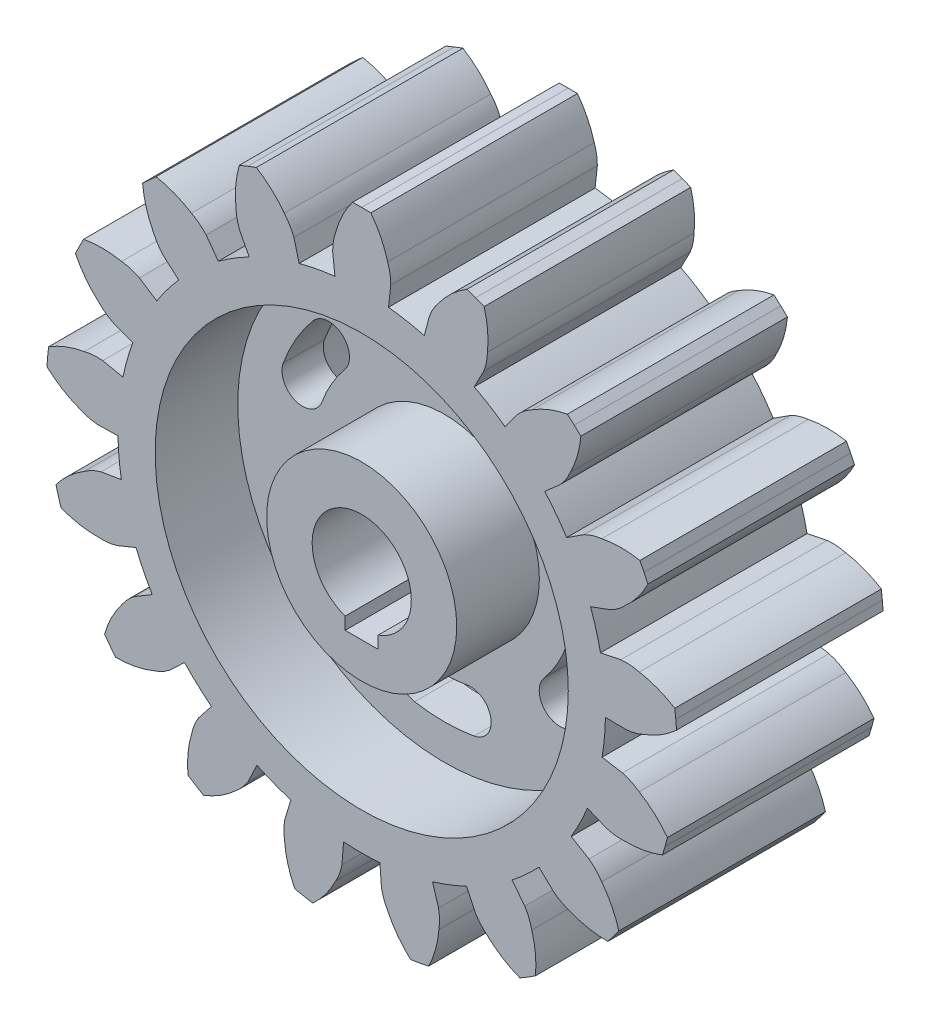
SolidWorks part; units mm, degrees
ref_plane "Plano frontal" through (0, 0, 0) normal (0, 0, 1) x (1, 0, 0)
ref_plane "Plano superior" through (0, 0, 0) normal (0, 1, 0) x (1, 0, 0)
ref_plane "Plano direito" through (0, 0, 0) normal (1, 0, 0) x (0, 0, -1)
sketch "Esboço1" plane through (0, 0, 0) normal (0, 0, 1) x (1, 0, 0)
  line L0 (4, -11.3137) -> (4, -14.3137)
  line L1 (4, -14.3137) -> (-4, -14.3137)
  line L2 (-4, -14.3137) -> (-4, -11.3137)
  line L3 (0, 36.5) -> (0, 0) construction
  line L4 (0, -1000) -> (0, 49000) construction
  line L5 (-6.4826, 58.6428) -> (-7.032, 63.6125)
  line L6 (-2.2097, 76.308) -> (0, 76.34)
  line L7 (6.4826, 58.6428) -> (7.032, 63.6125)
  line L8 (2.2097, 76.308) -> (0, 76.34)
  arc A0 (4, -11.3137) -> (-4, -11.3137) centre (0, 0) ccw
  circle A1 centre (0, 0) radius 23
  circle A2 centre (0, 0) radius 36.5 construction
  circle A3 centre (0, 0) radius 50
  circle A4 centre (0, 0) radius 59
  circle A5 centre (0, 0) radius 64 construction
  circle A6 centre (0, 0) radius 68.34 construction
  circle A7 centre (0, 0) radius 76.34 construction
  arc A8 (-6.3382, 35.9455) -> (6.3382, 35.9455) centre (0, 0) cw construction
  arc A13 (7.2064, 40.8695) -> (-7.2064, 40.8695) centre (0, 0) ccw
  arc A14 (5.4699, 31.0214) -> (-5.4699, 31.0214) centre (0, 0) ccw
  arc A15 (5.4699, 31.0214) -> (7.2064, 40.8695) centre (6.3382, 35.9455) ccw
  arc A16 (-7.2064, 40.8695) -> (-5.4699, 31.0214) centre (-6.3382, 35.9455) ccw
  arc A17 (29.6003, 10.7736) -> (24.1304, 20.2478) centre (0, 0) ccw
  arc A18 (29.6003, 10.7736) -> (38.9972, 14.1938) centre (34.2988, 12.4837) ccw
  arc A19 (31.7908, 26.6757) -> (24.1304, 20.2478) centre (27.9606, 23.4617) ccw
  arc A20 (38.9972, 14.1938) -> (31.7908, 26.6757) centre (0, 0) ccw
  arc A21 (27.9606, 23.4617) -> (34.2988, 12.4837) centre (0, 0) cw construction
  arc A22 (24.1304, -20.2478) -> (29.6003, -10.7736) centre (0, 0) ccw
  arc A23 (24.1304, -20.2478) -> (31.7908, -26.6757) centre (27.9606, -23.4617) ccw
  arc A24 (38.9972, -14.1938) -> (29.6003, -10.7736) centre (34.2988, -12.4837) ccw
  arc A25 (31.7908, -26.6757) -> (38.9972, -14.1938) centre (0, 0) ccw
  arc A26 (34.2988, -12.4837) -> (27.9606, -23.4617) centre (0, 0) cw construction
  arc A27 (-5.4699, -31.0214) -> (5.4699, -31.0214) centre (0, 0) ccw
  arc A28 (-5.4699, -31.0214) -> (-7.2064, -40.8695) centre (-6.3382, -35.9455) ccw
  arc A29 (7.2064, -40.8695) -> (5.4699, -31.0214) centre (6.3382, -35.9455) ccw
  arc A30 (-7.2064, -40.8695) -> (7.2064, -40.8695) centre (0, 0) ccw
  arc A31 (6.3382, -35.9455) -> (-6.3382, -35.9455) centre (0, 0) cw construction
  arc A32 (-29.6003, -10.7736) -> (-24.1304, -20.2478) centre (0, 0) ccw
  arc A33 (-29.6003, -10.7736) -> (-38.9972, -14.1938) centre (-34.2988, -12.4837) ccw
  arc A34 (-31.7908, -26.6757) -> (-24.1304, -20.2478) centre (-27.9606, -23.4617) ccw
  arc A35 (-38.9972, -14.1938) -> (-31.7908, -26.6757) centre (0, 0) ccw
  arc A36 (-27.9606, -23.4617) -> (-34.2988, -12.4837) centre (0, 0) cw construction
  arc A37 (-24.1304, 20.2478) -> (-29.6003, 10.7736) centre (0, 0) ccw
  arc A38 (-24.1304, 20.2478) -> (-31.7908, 26.6757) centre (-27.9606, 23.4617) ccw
  arc A39 (-38.9972, 14.1938) -> (-29.6003, 10.7736) centre (-34.2988, 12.4837) ccw
  arc A40 (-31.7908, 26.6757) -> (-38.9972, 14.1938) centre (0, 0) ccw
  arc A41 (-34.2988, 12.4837) -> (-27.9606, 23.4617) centre (0, 0) cw construction
  arc A42 (-7.032, 63.6125) -> (-6.28, 68.0508) centre (5.6072, 63.7539) cw
  arc A43 (-6.28, 68.0508) -> (-2.2097, 76.308) centre (17.0285, 61.693) cw
  arc A44 (7.032, 63.6125) -> (6.28, 68.0508) centre (-5.6072, 63.7539) ccw
  arc A45 (6.28, 68.0508) -> (2.2097, 76.308) centre (-17.0285, 61.693) ccw
  point P15 (0, 36.5)
  point P16 (0, -14.3137)
  point P28 (31.6099, 18.25)
  point P35 (31.6099, -18.25)
  point P42 (0, -36.5)
  point P49 (-31.6099, -18.25)
  point P56 (-31.6099, 18.25)
  point P61 (0, 0)
  dimension "D1" = 24
  dimension "D2" = 46
  dimension "D3" = 73
  dimension "D4" = 100
  dimension "D5" = 118
  dimension "D6" = 128
  dimension "D7" = 136.68
  dimension "D8" = 152.68
  dimension "D11" = 10
  dimension "D13" = 6
  dimension "D14" = 12.64
  dimension "D15" = 24.16
  dimension "D16" = 12.56
  dimension "D9" = 3
  dimension "D10" = 8
  dimension "D12" = 20
extrude "Ressalto-extrusão2" add sketch "Esboço1" along normal mid plane 50 contours A1 A0 L0 L1 L2 | A4 A3 region at (0, 57.3312, 0) region at (-22.3495, 0, 0)
extrude "Ressalto-extrusão3" add sketch "Esboço1<6>" along normal mid plane 10 contours A3 A40 A38 A37 A39 A35 A33 A32 A34 A30 A28 A27 A29 A25 A23 A22 A24 A20 A18 A17 A19 A16 A13 A15 A14 A1 region at (-48.5858, 0, 0)
sketch "Esboço1<6>" plane through (0, 0, 0) normal (0, 0, 1) x (1, 0, 0) same geometry as "Esboço1"
extrude "Ressalto-extrusão4" add sketch "Esboço1<7>" along normal mid plane 50 contours A44 A45 L8 L6 A43 A42 L5 A4 L7 region at (0, 66.5321, 0)
sketch "Esboço1<7>" plane through (0, 0, 0) normal (0, 0, 1) x (1, 0, 0) same geometry as "Esboço1"
pattern_circular "PadrãoCircular1" count 17 over 360 about axis through (0, 0, 25) along (0, 0, 1) of "Ressalto-extrusão4"
